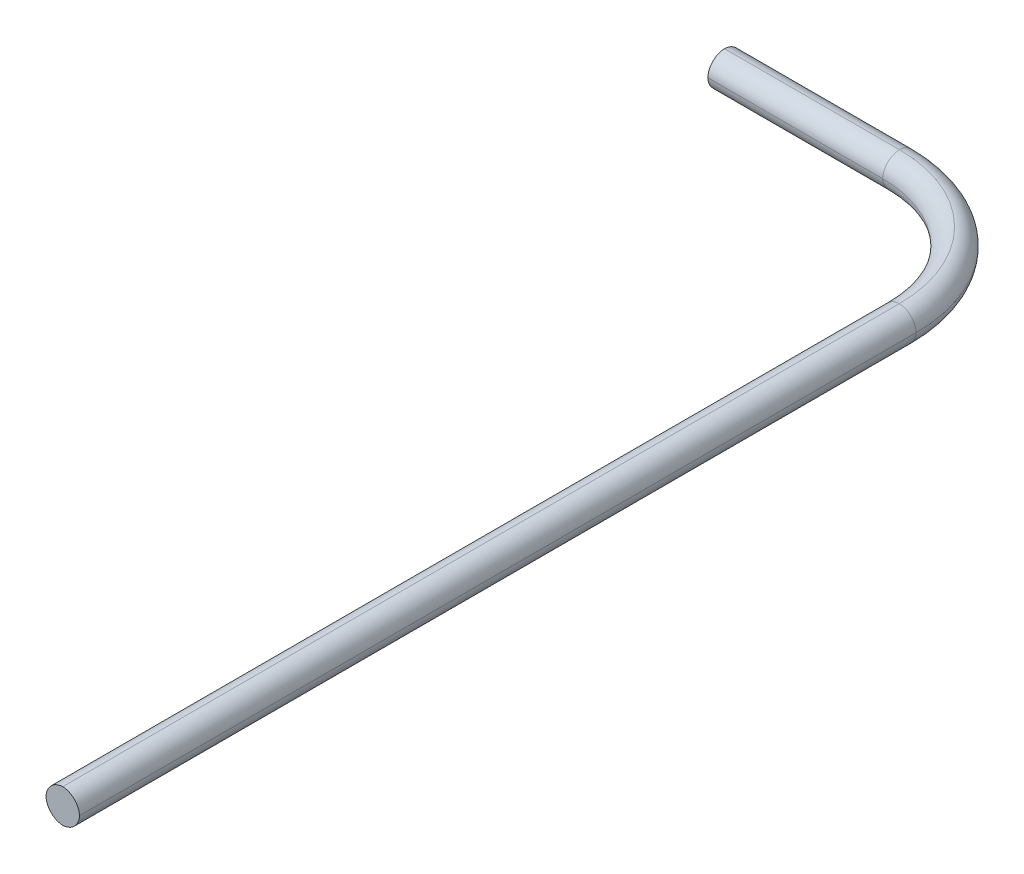
SolidWorks part; units mm, degrees
ref_plane "Front Plane" through (0, 0, 0) normal (0, 0, 1) x (1, 0, 0)
ref_plane "Top Plane" through (0, 0, 0) normal (0, 1, 0) x (1, 0, 0)
ref_plane "Right Plane" through (0, 0, 0) normal (1, 0, 0) x (0, 0, -1)
sketch "Sketch1" plane through (0, 0, 0) normal (0, 0, 1) x (1, 0, 0)
  line L1 (-5.75, 5.75) -> (5.75, 5.75)
  line L2 (-5.75, 5.75) -> (-5.75, -5.75)
  line L3 (-5.75, -5.75) -> (5.75, -5.75)
  line L4 (5.75, 5.75) -> (5.75, -5.75)
  line L5 (-5.75, 5.75) -> (5.75, -5.75) construction
  line L6 (-5.75, -5.75) -> (5.75, 5.75) construction
  point P0 (0, 0)
  dimension "D1" = 11.5
  dimension "D2" = 11.5
extrude "Boss-Extrude1" add sketch "Sketch1" along normal blind 338.5
sketch "Sketch2" plane through (-5.75, 0, 0) normal (-1, 0, 0) x (0, 0, 1)
  line L0 (338.5, 5.75) -> (0, 5.75) construction
  line L1 (0, -5.75) -> (11.5, -5.75)
  line L2 (0, -5.75) -> (0, 5.75)
  line L3 (0, 5.75) -> (11.5, 5.75)
  line L4 (11.5, -5.75) -> (11.5, 5.75)
  dimension "D1" = 11.5
extrude "Boss-Extrude2" add sketch "Sketch2" along normal blind 100
fillet "Fillet1" radius 40 1 edges at (-5.75, 0, 11.5)
fillet "Fillet2" radius 51.5 1 edges at (5.75, 0, 0)
fillet "Fillet3" radius 6 12 edges at (-5.75, -5.75, 195) (-17.4657, -5.75, 23.2157) (-5.75, 5.75, 195) (-17.4657, 5.75, 23.2157) (5.75, -5.75, 195) (-9.334, -5.75, 15.084) (5.75, 5.75, 195) (-9.334, 5.75, 15.084) (-75.75, -5.75, 11.5) (-75.75, 5.75, 11.5) (-75.75, -5.75, 0) (-75.75, 5.75, 0)
sketch "Sketch3" plane through (0, 0, 0) normal (0, 1, 0) x (1, 0, 0)
  line L0 (0, -111.6109) -> (-69.9543, -111.6109)
  line L1 (0, -338.5) -> (0, -51.5) construction
  line L2 (-69.9543, -111.6109) -> (-69.9543, 36.4493)
  line L3 (-69.9543, 36.4493) -> (-108.3599, 36.4493)
